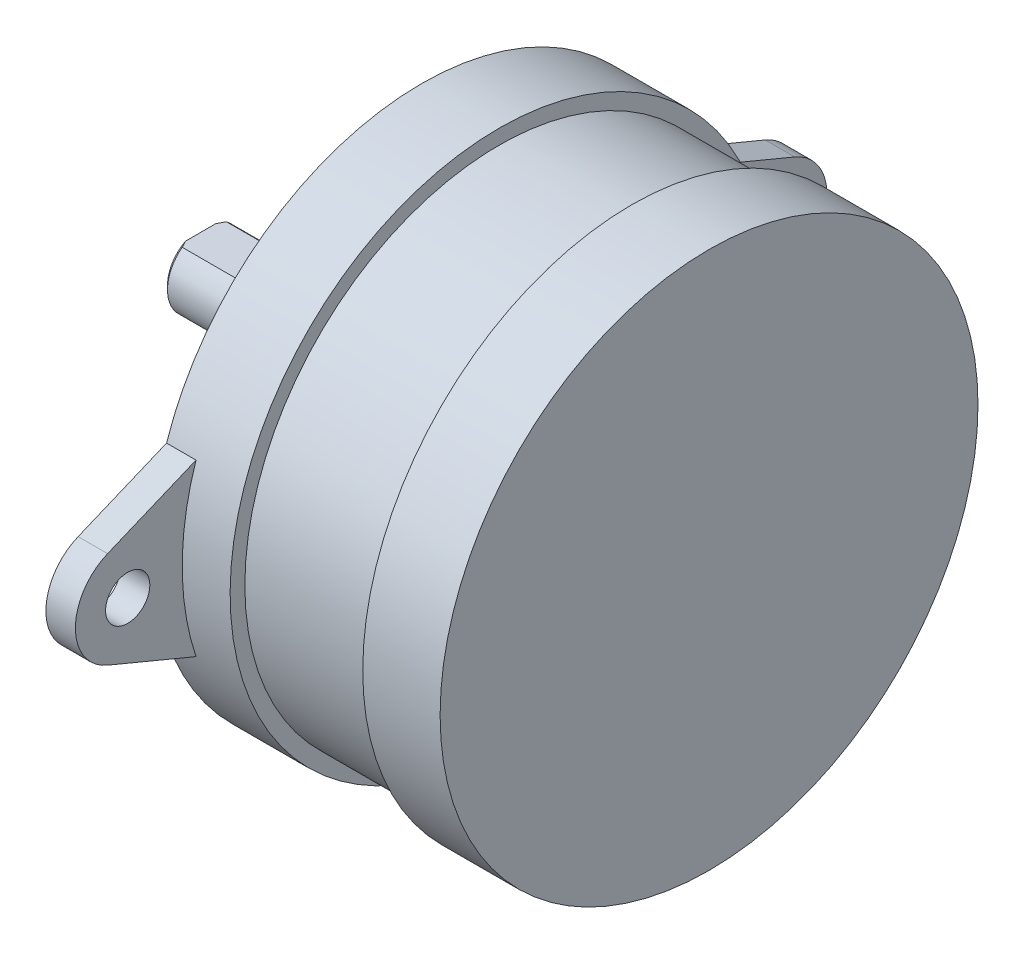
SolidWorks part; units mm, degrees
material "Acier non allié"
ref_plane "Plan de face" through (0, 0, 0) normal (0, 0, 1) x (1, 0, 0)
ref_plane "Plan de dessus" through (0, 0, 0) normal (0, 1, 0) x (1, 0, 0)
ref_plane "Plan de droite" through (0, 0, 0) normal (1, 0, 0) x (0, 0, -1)
sketch "Esquisse2" plane through (0, 0, 0) normal (1, 0, 0) x (0, 0, -1)
  circle A0 centre (0, 0) radius 18.25
  dimension "D1" = 36.5
extrude "Boss.-Extru.1" add sketch "Esquisse2" along normal blind 5.25
sketch "Esquisse3" plane through (5.25, 0, 0) normal (1, 0, 0) x (0, 0, -1)
  circle A0 centre (0, 0) radius 17.25
  dimension "D1" = 34.5
extrude "Boss.-Extru.2" add sketch "Esquisse3" along normal blind 9
sketch "Esquisse4" plane through (14.25, 0, 0) normal (1, 0, 0) x (0, 0, -1)
  circle A0 centre (0, 0) radius 18.25
  dimension "D1" = 36.5
extrude "Boss.-Extru.3" add sketch "Esquisse4" along normal blind 5.25
sketch "Esquisse6" plane through (0, 0, 0) normal (-1, 0, 0) x (0, 0, 1)
  line L0 (0, 0) -> (21.95, 0) construction
  line L1 (0, 0) -> (0, 18.25) construction
  line L2 (21.95, 0) -> (23.3137, 3.2776) construction
  line L3 (21.95, 0) -> (25.5, 0) construction
  line L4 (23.3137, 3.2776) -> (17.3124, 5.7745)
  line L5 (23.3137, -3.2776) -> (17.3124, -5.7745)
  line L6 (-23.3137, 3.2776) -> (-17.3124, 5.7745)
  line L7 (-23.3137, -3.2776) -> (-17.3124, -5.7745)
  circle A0 centre (0, 0) radius 18.25 construction
  circle A1 centre (21.95, 0) radius 1.5
  arc A2 (23.3137, 3.2776) -> (23.3137, -3.2776) centre (21.95, 0) cw
  arc A3 (17.3124, 5.7745) -> (17.294, -5.8292) centre (0, 0) cw
  circle A4 centre (-21.95, 0) radius 1.5
  arc A5 (-23.3137, 3.2776) -> (-23.3137, -3.2776) centre (-21.95, 0) ccw
  arc A6 (-17.3124, 5.7745) -> (-17.294, -5.8292) centre (0, 0) ccw
  circle M5 centre (0, 0) radius 18.25
  dimension "D3" = 3
  dimension "D1" = 21.95
  dimension "D2" = 25.5
  dimension "D4" = 6.5
extrude "Boss.-Extru.4" add sketch "Esquisse6" against normal blind 2 contours A2 L4 L5 A1 M5 | L6 A5 L7 A4 M5 region at (0, 0, 25.3584) region at (0, 0, -18.3916)
sketch "Esquisse7" plane through (0, 0, 0) normal (-1, 0, 0) x (0, 0, 1)
  circle A0 centre (0, 0) radius 8
  dimension "D1" = 16
extrude "Boss.-Extru.5" add sketch "Esquisse7" along normal blind 2
sketch "Esquisse8" plane through (0, 0, 0) normal (-1, 0, 0) x (0, 0, 1)
  circle A0 centre (0, 0) radius 2.5
  dimension "D1" = 5
extrude "Boss.-Extru.6" add sketch "Esquisse8" along normal blind 15
chamfer "Chanfrein1" distance 0.25 angle 45 1 edges at (-15, 0, 2.5)
sketch "Esquisse9" plane through (-15, 0, 0) normal (-1, 0, 0) x (0, 0, 1)
  line L1 (-2.5, 2) -> (2.5, 2)
  line L2 (-2.5, 2) -> (-2.5, 3)
  line L3 (-2.5, 3) -> (2.5, 3)
  line L4 (2.5, 2) -> (2.5, 3)
  dimension "D1" = 5
  dimension "D2" = 2.5
  dimension "D3" = 2
  dimension "D4" = 1
extrude "Enlèv. mat.-Extru.1" cut sketch "Esquisse9" against normal blind 10
